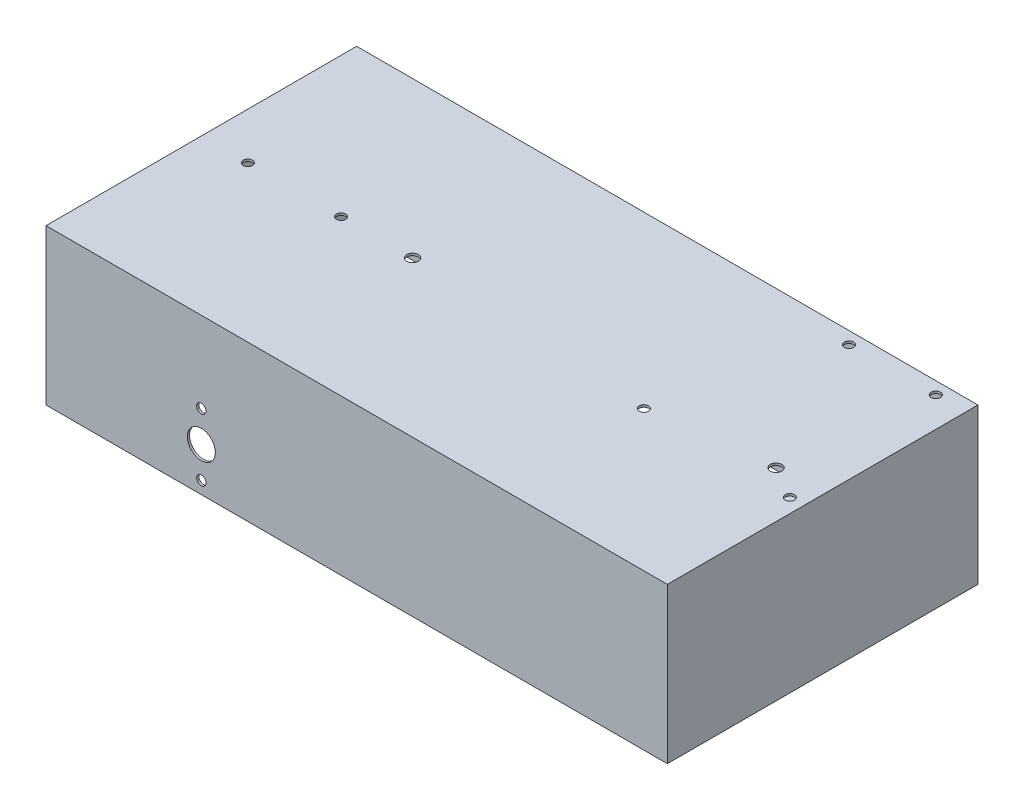
SolidWorks part; units mm, degrees
ref_plane "Front Plane" through (0, 0, 0) normal (0, 0, 1) x (1, 0, 0)
ref_plane "Top Plane" through (0, 0, 0) normal (0, 1, 0) x (1, 0, 0)
ref_plane "Right Plane" through (0, 0, 0) normal (1, 0, 0) x (0, 0, -1)
sketch "Sketch1" plane through (0, 0, 0) normal (0, 1, 0) x (1, 0, 0)
  line L1 (0, 50) -> (200, 50)
  line L2 (0, 50) -> (0, -50)
  line L3 (0, -50) -> (200, -50)
  line L4 (200, 50) -> (200, -50)
  point P4 (0, 0)
  dimension "D1" = 200
  dimension "D2" = 100
extrude "Boss-Extrude1" add sketch "Sketch1" along normal blind 50
sketch "Sketch2" plane through (0, 0, 50) normal (0, 0, 1) x (1, 0, 0)
  line L0 (0, 50) -> (0, 0) construction
  line L1 (50, 24) -> (50, 4) construction
  line L2 (0, 50) -> (200, 50) construction
  circle A0 centre (50, 14) radius 4.5
  circle A1 centre (50, 4) radius 1.5
  circle A2 centre (50, 24) radius 1.5
  point P0 (50, 14)
  point P9 (50, 14)
  dimension "D3" = 9
  dimension "D4" = 3
  dimension "D1" = 50
  dimension "D2" = 36
  dimension "D5" = 20
sketch "Sketch3" plane through (0, 0, 0) normal (0, -1, 0) x (1, 0, 0)
  line L0 (0.7, 49.3) -> (0.7, -49.3)
  line L1 (0.7, -49.3) -> (199.3, -49.3)
  line L2 (199.3, -49.3) -> (199.3, 49.3)
  line L3 (199.3, 49.3) -> (0.7, 49.3)
  line L4 (0, 50) -> (0, -50)
  line L5 (0, -50) -> (200, -50)
  line L6 (200, -50) -> (200, 50)
  line L7 (200, 50) -> (0, 50)
  line L8 (0, 50) -> (0, -50) construction
  line L9 (0, -50) -> (200, -50) construction
  line L10 (200, -50) -> (200, 50) construction
  line L11 (200, 50) -> (0, 50) construction
  dimension "D1" = 0
  dimension "D2" = 0.7
extrude "Cut-Extrude1" cut sketch "Sketch3" against normal offset from surface (49.3 mm away) 0.7 up to face at (100, 50, 0)
sketch "Sketch4" plane through (0, 0, 0) normal (0, -1, 0) x (1, 0, 0)
  line L0 (0.7, -49.3) -> (199.3, -49.3) construction
  line L1 (145, -49.3) -> (199.3, -49.3)
  line L2 (145, -49.3) -> (145, 49.3)
  line L3 (145, 49.3) -> (199.3, 49.3)
  line L4 (199.3, -49.3) -> (199.3, 49.3)
  line L5 (199.3, 49.3) -> (0.7, 49.3) construction
  line L6 (160, -47.9) -> (160, 49.3) construction
  line L7 (200, -50) -> (200, 50) construction
  line L8 (199.3, -49.3) -> (199.3, 49.3) construction
  circle A0 centre (160, 0.7) radius 11.43 construction
  point P12 (160, 0.7)
  dimension "D3" = 22.86
  dimension "D1" = 40
  dimension "D2" = 55
  dimension "D4" = 50
extrude "Boss-Extrude2" add sketch "Sketch4" against normal blind 0.7
extrude "Cut-Extrude2" cut sketch "Sketch2" against normal through all
sketch "Sketch6" plane through (0, 0, 50) normal (0, 0, 1) x (1, 0, 0)
  line L0 (4.6, 50) -> (4.6, 0) construction
  line L1 (0, 50) -> (200, 50) construction
  line L2 (200, 0) -> (0, 0) construction
  line L3 (0, 45) -> (200, 45) construction
  line L4 (0, 50) -> (0, 0) construction
  line L5 (200, 50) -> (200, 0) construction
  line L6 (0, 35) -> (200, 35) construction
  line L7 (54.1, 45) -> (54.1, 35) construction
  line L8 (69.1, 45) -> (69.1, 35) construction
  circle A0 centre (4.6, 45) radius 1.5
  circle A1 centre (4.6, 35) radius 1.5
  circle A2 centre (54.1, 45) radius 1.5
  circle A3 centre (54.1, 35) radius 1.5
  circle A4 centre (69.1, 45) radius 1.5
  circle A5 centre (69.1, 35) radius 1.5
  dimension "D1" = 3
  dimension "D3" = 5
  dimension "D4" = 10
  dimension "D5" = 4.6
  dimension "D6" = 15
  dimension "D7" = 54.1
extrude "Cut-Extrude3" [suppressed] cut sketch "Sketch6" against normal up to surface (0.7 mm away) up to face at (51.5, 4, 49.3)
sketch "Sketch7" plane through (0, 0, 0) normal (-1, 0, 0) x (0, 0, 1)
  line L0 (42, 50) -> (42, 0) construction
  line L1 (-50, 50) -> (50, 50) construction
  line L2 (-50, 0) -> (50, 0) construction
  circle A0 centre (42, 45) radius 1.5
  circle A1 centre (42, 35) radius 1.5
  dimension "D4" = 3
  dimension "D1" = 8
  dimension "D2" = 5
  dimension "D3" = 10
extrude "Cut-Extrude4" [suppressed] cut sketch "Sketch7" against normal up to surface (0.7 mm away) up to face at (0.7, 24.65, 0)
sketch "Sketch8" plane through (0, 0, 0) normal (0, -1, 0) x (1, 0, 0)
  line L0 (160, -47.9) -> (160, 49.3) construction
  circle A0 centre (160, 8.45) radius 1.21
  circle A1 centre (160, -7.05) radius 1.21
  dimension "D2" = 2.42
  dimension "D1" = 7.75
  dimension "D3" = 7.75
extrude "Cut-Extrude6" cut sketch "Sketch8" against normal blind 1.8 contours A1 | A0
sketch "Sketch9" plane through (0, 50, 0) normal (0, 1, 0) x (1, 0, 0)
  line L0 (0, 0) -> (200, 0) construction
  line L1 (200, 50) -> (200, -50) construction
  circle A0 centre (15, 0) radius 1.5
  circle A1 centre (45, 0) radius 1.5
  dimension "D1" = 3
  dimension "D2" = 15
  dimension "D3" = 30
sketch "Sketch10" plane through (0, 49.3, 0) normal (0, -1, 0) x (1, 0, 0)
  line L0 (0, 0) -> (200, 0)
  line L1 (200, -50) -> (200, 50) construction
  circle A0 centre (185, 0) radius 1.87
  circle A1 centre (68, 0) radius 1.87
  dimension "D2" = 3.74
  dimension "D1" = 117
  dimension "D3" = 15
extrude "Cut-Extrude8" cut sketch "Sketch10" against normal up to surface (0.7 mm away) contours A0 | A1 up to face at (100, 50, 0)
extrude "Cut-Extrude7" cut sketch "Sketch9" against normal through all
sketch "Sketch11" plane through (143.38, 50, -175.08) normal (0, 1, 0) x (0, 0, 1)
  line L6 (129.04, 19.06) -> (129.04, 47) construction
  circle A0 centre (129.04, 47) radius 1.5
  circle A1 centre (181.11, 52.08) radius 1.5
  circle A2 centre (179.84, 3.82) radius 1.5
  circle A3 centre (129.04, 19.06) radius 1.5
  point P12 (195.08, 54.62)
  dimension "D8" = 3
  dimension "D1" = 13.97
  dimension "D2" = 66.04
  dimension "D3" = 15.24
  dimension "D4" = 2.54
  dimension "D5" = 7.62
  dimension "D6" = 50.8
  dimension "D7" = 35.56
  dimension "D9" = 70
  dimension "D10" = 2
extrude "Cut-Extrude9" cut sketch "Sketch11" against normal up to surface (0.7 mm away) up to face at (15, 49.3, 1.5)
